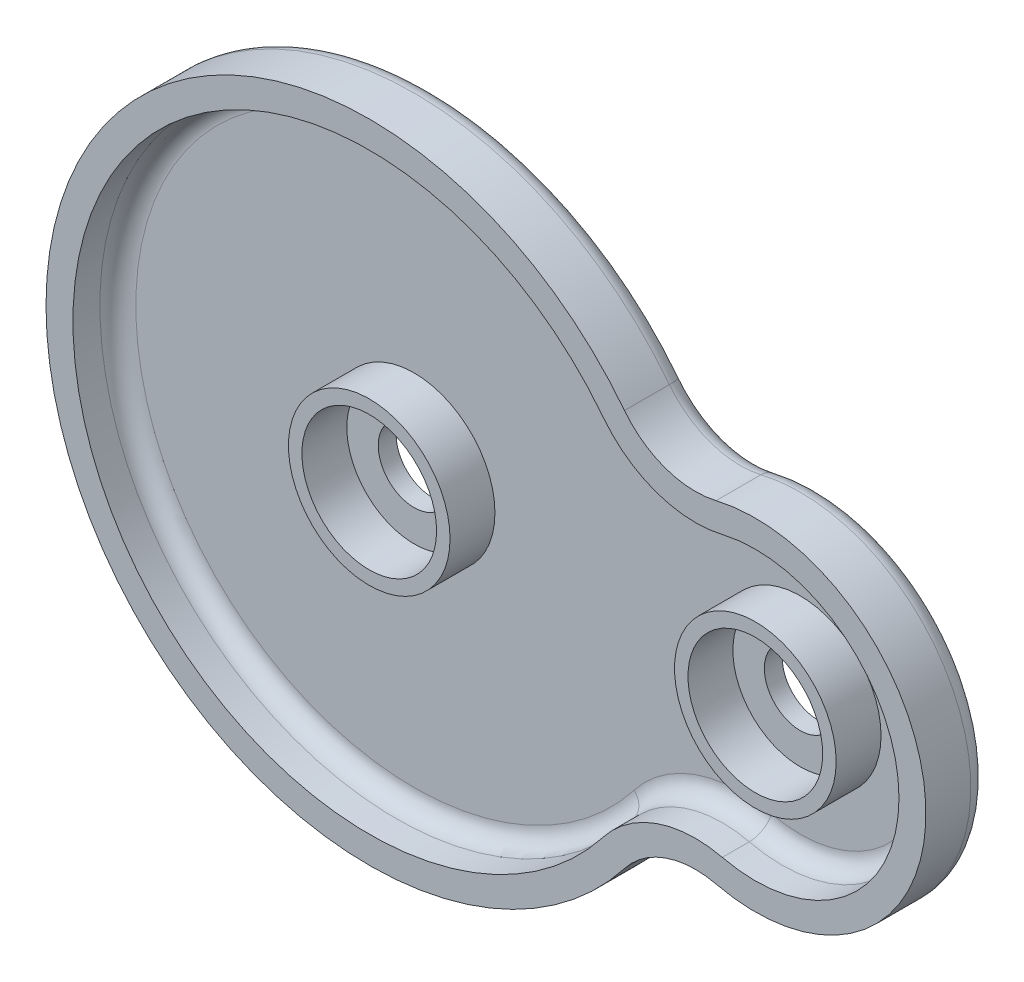
SolidWorks part; units mm, degrees
material "Stainless Steel (ferritic)"
ref_plane "Front Plane" through (0, 0, 0) normal (0, 0, 1) x (1, 0, 0)
ref_plane "Top Plane" through (0, 0, 0) normal (0, 1, 0) x (1, 0, 0)
ref_plane "Right Plane" through (0, 0, 0) normal (1, 0, 0) x (0, 0, -1)
sketch "Sketch1" plane through (0, 0, 0) normal (0, 0, 1) x (1, 0, 0)
  circle A0 centre (0, 0) radius 7.5
  circle A1 centre (0, 0) radius 4
  circle A2 centre (0, 0) radius 9
  circle A3 centre (43, 0) radius 9
  circle A4 centre (43, 0) radius 4
  circle A5 centre (43, 0) radius 7.5
  arc A6 (28.4287, 22.0864) -> (28.4287, -22.0864) centre (0, 0) ccw
  arc A8 (38.6271, -18.4899) -> (38.6271, 18.4899) centre (43, 0) ccw
  arc A9 (35.6279, 5.1626) -> (32.3721, 15.7495) centre (0, 0) ccw construction
  arc A10 (32.3721, -15.7495) -> (35.6279, -5.1626) centre (0, 0) ccw construction
  arc A11 (35.9157, 2.4622) -> (35.6279, 5.1626) centre (0, 0) ccw construction
  arc A12 (35.6279, -5.1626) -> (35.9157, -2.4622) centre (0, 0) ccw construction
  arc A13 (35.9157, -2.4622) -> (35.9157, 2.4622) centre (0, 0) ccw construction
  arc A14 (32.3721, 15.7495) -> (32.3721, -15.7495) centre (43, 0) ccw construction
  arc A15 (28.4287, -22.0864) -> (38.6271, -18.4899) centre (36.3256, -28.2215) cw
  arc A16 (28.4287, 22.0864) -> (38.6271, 18.4899) centre (36.3256, 28.2215) ccw
  arc A17 (26.0597, 20.2458) -> (26.0597, -20.2458) centre (0, 0) ccw
  arc A18 (26.0597, -20.2458) -> (39.3176, -15.5705) centre (36.3256, -28.2215) cw
  arc A19 (39.3176, -15.5705) -> (39.3176, 15.5705) centre (43, 0) ccw
  arc A20 (26.0597, 20.2458) -> (39.3176, 15.5705) centre (36.3256, 28.2215) ccw
  dimension "D1" = 8
  dimension "D2" = 15
  dimension "D3" = 18
  dimension "D5" = 72
  dimension "D6" = 38
  dimension "D7" = 10
  dimension "D4" = 43
  dimension "D8" = 3
extrude "Boss-Extrude1" add sketch "Sketch1" along normal blind 2 contours A16 A6 A15 A8 A17 A20 A19 A18 | A20 A17 A18 A19 A3 A2 | A0 A1 | A2 A0 | A5 A4 | A3 A5 region at (-7.2879, 0, 0) region at (-8.7454, 0, 0) region at (34.2546, 0, 0) region at (35.7121, 0, 0) region at (32.5954, 17.6439, 0) region at (31.6256, 14.8937, 0)
extrude "Boss-Extrude2" add sketch "Sketch1<3>" along normal blind 7 contours A2 A0 | A3 A5 region at (-8.7454, 0, 0) region at (34.2546, 0, 0)
sketch "Sketch1<3>" plane through (0, 0, 0) normal (0, 0, 1) x (1, 0, 0) same geometry as "Sketch1"
extrude "Boss-Extrude3" add sketch "Sketch1<4>" along normal blind 7 contours A16 A6 A15 A8 A17 A20 A19 A18 region at (32.5954, 17.6439, 0)
sketch "Sketch1<4>" plane through (0, 0, 0) normal (0, 0, 1) x (1, 0, 0) same geometry as "Sketch1"
fillet "Fillet1" radius 2 8 edges at (32.9998, -18.7907, 0) (-36, 0, 0) (32.9998, 18.7907, 0) (32.0021, -15.9615, 2) (59, 0, 2) (32.0021, 15.9615, 2) (62, 0, 0) (-33, 0, 2)
